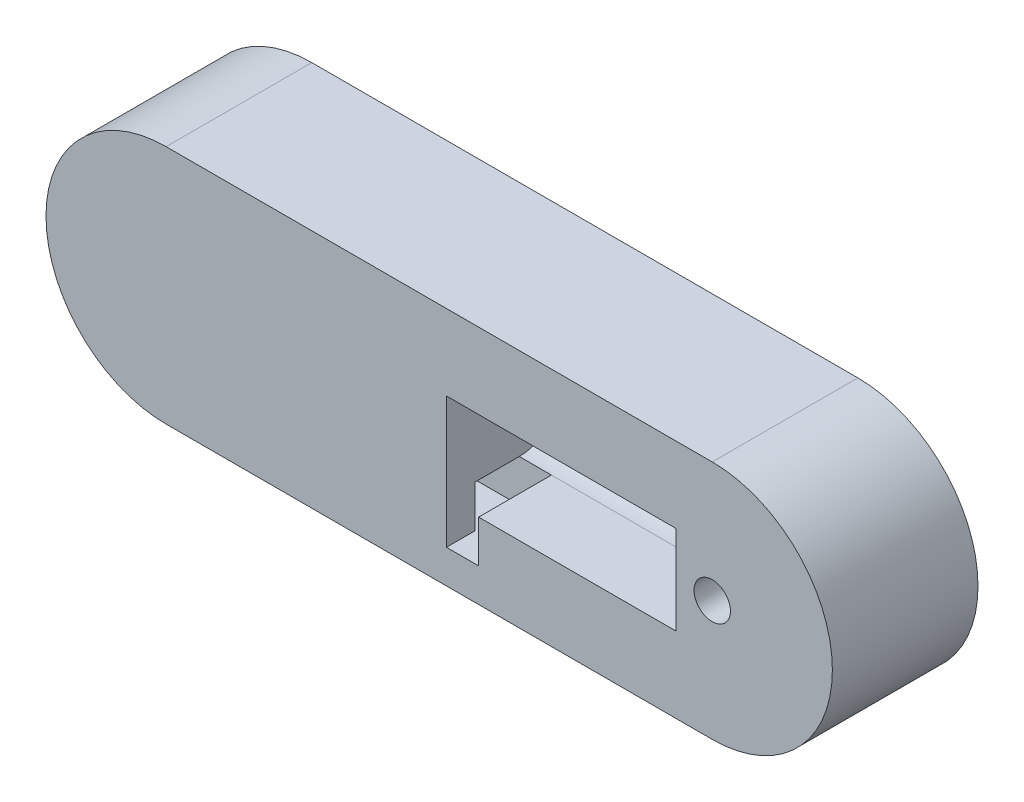
SolidWorks part; units mm, degrees
note: The reader was unsure of these and kept them because the rebuilt part matched: shared geometry of "Croquis1<4>".
ref_plane "Alzado" through (0, 0, 0) normal (0, 0, 1) x (1, 0, 0)
ref_plane "Planta" through (0, 0, 0) normal (0, 1, 0) x (1, 0, 0)
ref_plane "Vista lateral" through (0, 0, 0) normal (1, 0, 0) x (0, 0, -1)
sketch "Croquis1" plane through (0, 0, 0) normal (0, 0, 1) x (1, 0, 0)
  line L0 (-43.0271, -33) -> (106.9729, -33)
  line L1 (-43.0271, 33) -> (106.9729, 33)
  line L2 (-41.5099, 1.3031) -> (-41.5099, -1.3031)
  circle A0 centre (-43.0271, 0) radius 33
  circle A1 centre (106.9729, 0) radius 33
  circle A2 centre (-43.0271, 0) radius 2
  circle A3 centre (106.9729, 0) radius 5
  dimension "D2" = 4
  dimension "D3" = 10
  dimension "D4" = 66
  dimension "D1" = 150
extrude "Saliente-Extruir1" add sketch "Croquis1" along normal blind 40 contours A0 L0 A2 | A1 L1 A0 L0 | L1 A1 A3 | A2 | L2 A2
extrude "Cortar-Extruir2" cut sketch "Croquis1<4>" along normal blind 10 contours L2 A2
sketch "Croquis1<4>" plane through (0, 0, 0) normal (0, 0, 1) x (1, 0, 0) same geometry as "Croquis1"
sketch "Croquis5" plane through (0, 0, 40) normal (0, 0, 1) x (1, 0, 0)
  line L0 (42.8059, -23.8) -> (42.8059, -12.2)
  line L1 (42.8059, -12.2) -> (96.9729, -12.2)
  line L9 (33.9729, 12.2) -> (33.9729, -23.8)
  line L10 (96.9729, -12.2) -> (96.9729, 12.2)
  line L13 (33.9729, -23.8) -> (42.8059, -23.8)
  line L14 (96.9729, 12.2) -> (33.9729, 12.2)
  arc A0 (106.9729, -33) -> (106.9729, 33) centre (106.9729, 0) ccw construction
  arc A1 (106.9729, -33) -> (106.9729, 33) centre (106.9729, 0) ccw
  circle A2 centre (106.9729, 0) radius 5 construction
  circle A3 centre (106.9729, 0) radius 5
  point P2 (96.9729, 0)
  dimension "D2" = 10
  dimension "D3" = 63
  dimension "D4" = 24.4
  dimension "D1" = 11.6
extrude "Cortar-Extruir4" cut sketch "Croquis5" against normal blind 20 contours L10 L14 L9 L13 L0 L1
ref_plane "Plano2" through (33.9729, 0, 0) normal (1, 0, 0) x (0, 0, -1)
sketch "Croquis6" plane through (33.9729, 0, 0) normal (1, 0, 0) x (0, 0, -1)
  line L0 (-20, 12.2) -> (-40, 12.2)
  line L1 (-20, -12.2) -> (-40, -12.2)
  line L2 (-20, -23.8) -> (-20, -12.2)
  line L4 (-40, 12.2) -> (-40, -23.8)
  line L5 (-40, -23.8) -> (-20, -23.8)
  line L6 (-20, -23.8) -> (-20, 12.2)
  line L7 (-20, 12.2) -> (-40, 12.2)
  line L8 (-40, 12.2) -> (-40, -23.8)
  line L9 (-40, -23.8) -> (-20, -23.8)
  line L11 (-20, 12.2) -> (-40, 12.2)
  line L16 (0, -33) -> (0, 33)
  line L17 (0, 33) -> (-40, 33)
  line L18 (-40, 33) -> (-40, -33)
  line L19 (-40, -33) -> (0, -33)
  line L20 (0, -33) -> (0, 33)
  line L21 (0, 33) -> (-40, 33)
  line L22 (-40, 33) -> (-40, -33)
  line L23 (-40, -33) -> (0, -33)
  circle A0 centre (-20, 0) radius 12.2
  dimension "D2" = 24.4
  dimension "D3" = 0
  dimension "D1" = 0
extrude "Cortar-Extruir6" cut sketch "Croquis6" along direction (1, 0, 0) on the side of the normal up to surface (63 mm away) contours A0 | A0 L0 L8 L1
sketch "Croquis7" plane through (96.9729, 0, 0) normal (-1, 0, 0) x (0, 0, 1)
  line L1 (40, -12.2) -> (40.0638, -12.2)
  line L3 (20, -12.2) -> (7.8, -12.2)
  line L4 (20, -12.2) -> (20, 12.2) construction
  line L5 (20, 12.2) -> (7.8, 12.2)
  line L9 (40, 12.2) -> (40.0638, 12.2)
  line L11 (7.8, -12.2) -> (7.8, 12.2)
  line L12 (40, -12.2) -> (40, 12.2)
  line L13 (40, 12.2) -> (20, 12.2)
  line L16 (20, -12.2) -> (40, -12.2)
  line L17 (40, -12.2) -> (40, 12.2)
  line L22 (40, 12.2) -> (20, 12.2)
  line L26 (7.8, -12.2) -> (32.2, -12.2)
  line L27 (7.8, -12.2) -> (7.8, 12.2)
  line L28 (7.8, 12.2) -> (32.2, 12.2)
  line L29 (32.2, -12.2) -> (32.2, 12.2)
  line L34 (20, -12.2) -> (40, -12.2)
  circle A0 centre (20, 0) radius 12.2 construction
  arc A1 (20, 12.2) -> (20, -12.2) centre (20, 0) ccw
  arc A3 (20, 12.2) -> (20, -12.2) centre (20, 0) ccw construction
  arc M8 (20, 12.2) -> (20, -12.2) centre (20, 0) ccw
  line M9 (20, -12.2) -> (40, -12.2)
  dimension "D1" = 0
extrude "Cortar-Extruir9" cut sketch "Croquis7" against normal blind 30 contours L29 L22 M9 M8 | L11 L3 M8 | L11 L5 M8
sketch "Croquis8" plane through (33.9729, 0, 0) normal (1, 0, 0) x (0, 0, -1)
  line L0 (-32.2, -12.2) -> (-32.2, -23.8)
  line L4 (-32.2, -12.2) -> (-32.2, 12.2)
  line L5 (-40, -12.2) -> (-32.2, -12.2)
  line L6 (-40, 12.2) -> (-40, -12.2)
  line L7 (-32.2, 12.2) -> (-40, 12.2)
  line L8 (-40, -12.2) -> (-40, -23.8)
  line L9 (-20, -12.2) -> (-40, -12.2)
  line L10 (-20, -23.8) -> (-20, -12.2)
  line L11 (-40, -23.8) -> (-20, -23.8)
  line L12 (-40, -12.2) -> (-40, -23.8)
  line L13 (-20, -12.2) -> (-32.2, -12.2)
  line L14 (-20, -23.8) -> (-20, -12.2)
  line L15 (-40, -23.8) -> (-20, -23.8)
  line L18 (-40, 12.2) -> (-40, -12.2)
  line L19 (-32.2, 12.2) -> (-40, 12.2)
  line M10 (-40, -23.8) -> (-20, -23.8)
  line M11 (-20, -23.8) -> (-20, -12.2)
  dimension "D1" = 0
  dimension "D2" = 0
extrude "Cortar-Extruir10" cut sketch "Croquis8" against normal blind 66 contours L13 L0 M11 M10
sketch "Croquis9" plane through (0, 0, 0) normal (0, 0, -1) x (-1, 0, 0)
  line L0 (20.4271, -23.8) -> (20.4271, -12.2)
  line L8 (-33.9729, -12.2) -> (-33.9729, -23.8)
  line L9 (-33.9729, -23.8) -> (32.0271, -23.8)
  line L10 (32.0271, -23.8) -> (32.0271, -12.2)
  line L11 (32.0271, -12.2) -> (-33.9729, -12.2)
  line L13 (20.4271, -23.8) -> (32.0271, -23.8)
  line L14 (32.0271, -23.8) -> (32.0271, -12.2)
  line L15 (32.0271, -12.2) -> (20.4271, -12.2)
  dimension "D2" = 0
extrude "Cortar-Extruir11" cut sketch "Croquis9" against normal up to next
chamfer "Chaflán1" distance 10 angle 45 1 edges at (-32.0271, -18, 0)
